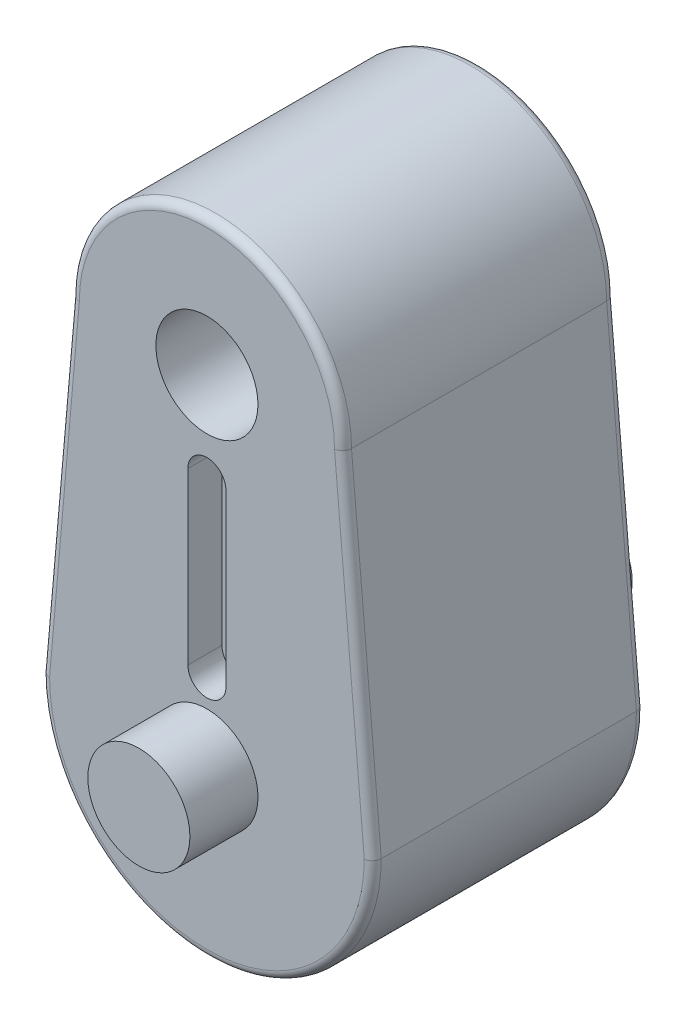
SolidWorks part; units mm, degrees
material "Cast Alloy Steel"
ref_plane "Front Plane" through (0, 0, 0) normal (0, 0, 1) x (1, 0, 0)
ref_plane "Top Plane" through (0, 0, 0) normal (0, 1, 0) x (1, 0, 0)
ref_plane "Right Plane" through (0, 0, 0) normal (1, 0, 0) x (0, 0, -1)
sketch "Sketch1" plane through (0, 0, 0) normal (0, 0, 1) x (1, 0, 0)
  line L0 (-101.6, 0) -> (-123.8221, -254)
  line L1 (101.6, 0) -> (123.8221, -254)
  line L2 (-101.6, 0) -> (-101.6, -254) construction
  line L3 (101.6, 0) -> (101.6, -254) construction
  arc A0 (101.6, 0) -> (-101.6, 0) centre (0, 0) ccw
  arc A1 (123.8221, -254) -> (-123.8221, -254) centre (0, -254) cw
  dimension "D1" = 101.6
  dimension "D2" = 254
  dimension "D3" = 254
  dimension "D4" = 5
  dimension "D5" = 5
extrude "Boss-Extrude2" add sketch "Sketch1" along normal blind 203.2 contours A0 L0 A1 L1
sketch "Sketch2" plane through (0, 0, 203.2) normal (0, 0, 1) x (1, 0, 0)
  circle A0 centre (0, 0) radius 38.1
  dimension "D1" = 76.2
extrude "Cut-Extrude3" cut sketch "Sketch2" against normal blind 203.2 contours A0
sketch "Sketch5" plane through (0, 0, 203.2) normal (0, 0, 1) x (1, 0, 0)
sketch "Sketch8" plane through (0, 0, 203.2) normal (0, 0, 1) x (1, 0, 0)
  circle A0 centre (0, -254) radius 38.1
  dimension "D2" = 76.2
  dimension "D1" = 254
extrude "Boss-Extrude6" add sketch "Sketch8" along normal blind 50.8 contours A0
sketch "Sketch9" plane through (0, 0, 0) normal (0, 0, -1) x (-1, 0, 0)
  circle A0 centre (0, -254) radius 38.1
  dimension "D2" = 76.2
  dimension "D1" = 254
extrude "Boss-Extrude7" add sketch "Sketch9" along normal blind 76.2
fillet "Fillet1" radius 6.35 8 edges at (-112.7111, -127, 203.2) (0, -377.8221, 203.2) (0, 101.6, 203.2) (112.7111, -127, 203.2) (0, -377.8221, 0) (-112.7111, -127, 0) (0, 101.6, 0) (112.7111, -127, 0)
sketch "Sketch10" plane through (0, 0, 203.2) normal (0, 0, 1) x (1, 0, 0)
  line L0 (0, -194.6013) -> (0, -67.6013) construction
  line L1 (-14.2071, -194.6013) -> (-14.2071, -67.6013)
  line L2 (14.2071, -194.6013) -> (14.2071, -67.6013)
  arc A0 (-14.2071, -194.6013) -> (14.2071, -194.6013) centre (0, -194.6013) ccw
  arc A1 (14.2071, -67.6013) -> (-14.2071, -67.6013) centre (0, -67.6013) ccw
  point P3 (0, -131.1013)
  dimension "D1" = 127
extrude "Cut-Extrude4" cut sketch "Sketch10" against normal blind 25.4
